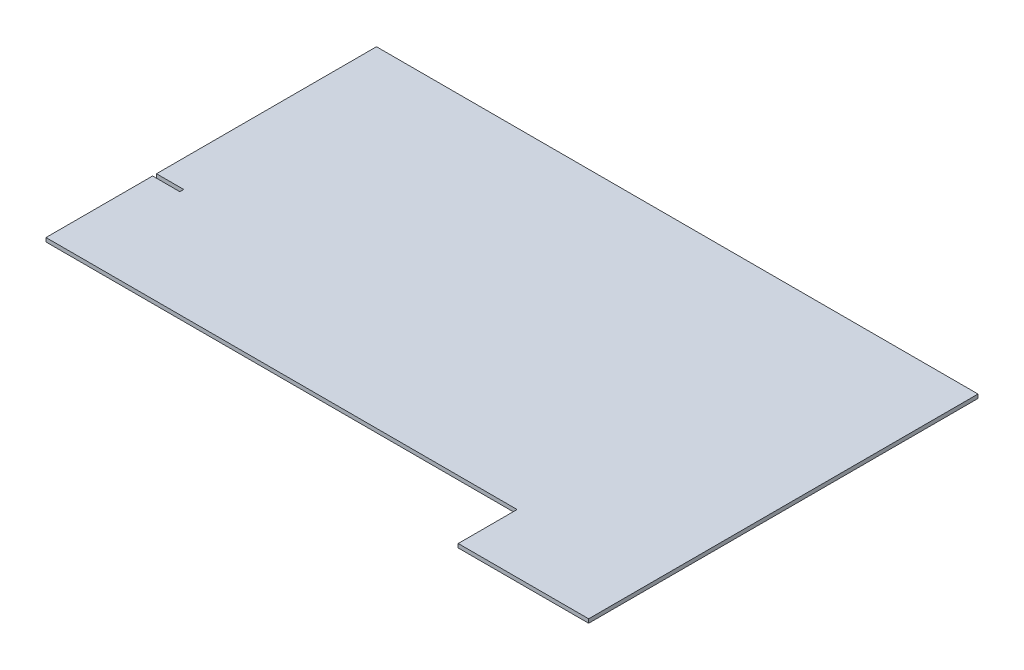
SolidWorks part; units mm, degrees
ref_plane "Front Plane" through (0, 0, 0) normal (0, 0, 1) x (1, 0, 0)
ref_plane "Top Plane" through (0, 0, 0) normal (0, 1, 0) x (1, 0, 0)
ref_plane "Right Plane" through (0, 0, 0) normal (1, 0, 0) x (0, 0, -1)
sketch "Sketch1" plane through (0, 0, 0) normal (0, 1, 0) x (1, 0, 0)
  line L0 (242, 0) -> (242, -30.24)
  line L1 (0, 0) -> (242, 0)
  line L2 (0, 0) -> (0, 169.76)
  line L3 (0, 169.76) -> (309, 169.76)
  line L4 (309, -30.24) -> (309, 169.76)
  line L5 (242, -30.24) -> (309, -30.24)
  dimension "D1" = 309
  dimension "D2" = 169.76
  dimension "D3" = 67
  dimension "D4" = 200
extrude "Boss-Extrude1" add sketch "Sketch1" along normal blind 2
sketch "Sketch2" plane through (0, 2, 0) normal (0, 1, 0) x (1, 0, 0)
  line L0 (0, 169.76) -> (0, 0) construction
  line L1 (0, 56.76) -> (14, 56.76)
  line L2 (0, 56.76) -> (0, 54.76)
  line L3 (0, 54.76) -> (14, 54.76)
  line L4 (14, 56.76) -> (14, 54.76)
  line L5 (309, 169.76) -> (0, 169.76) construction
  dimension "D1" = 2
  dimension "D2" = 14
  dimension "D3" = 113
extrude "Cut-Extrude1" cut sketch "Sketch2" against normal blind 10
